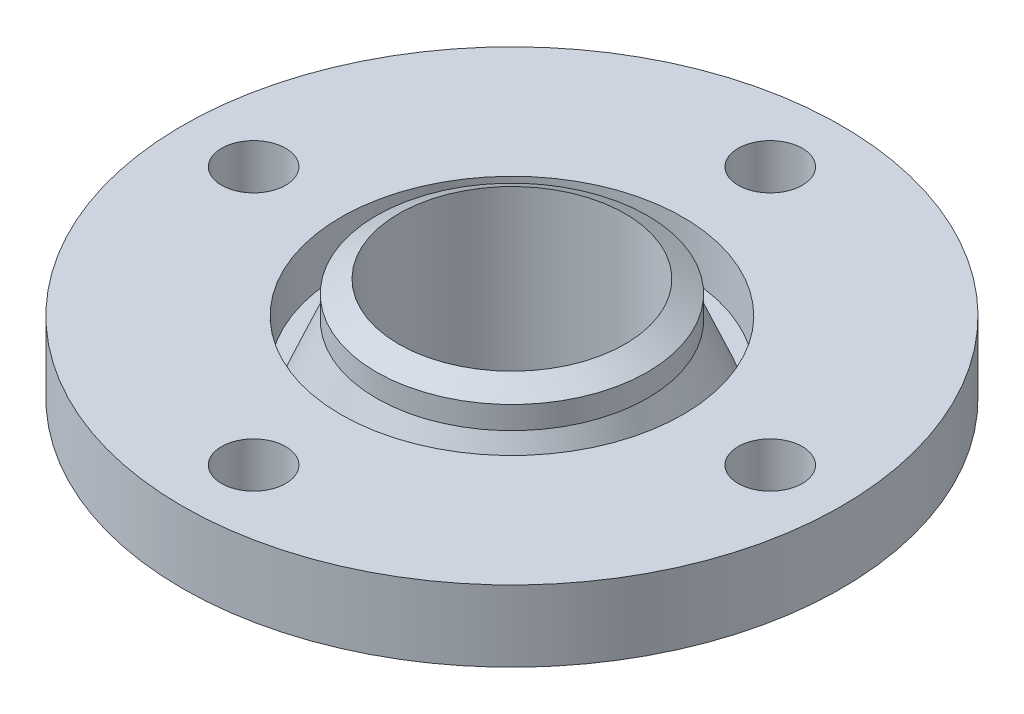
SolidWorks part; units mm, degrees
revolve "BaseRevolve" add sketch "BaseSketch" angle 360 about L0
sketch "BaseSketch" plane through (0, 0, 0) normal (0, 0, 1) x (1, 0, 0)
  line L0 (0, 0) -> (0, -80.3134) construction
  line L1 (-31.75, 0) -> (-31.75, -45)
  line L2 (-31.75, -45) -> (-59, -45)
  line L3 (-59, -45) -> (-59, -29)
  line L4 (-59, -29) -> (-92.5, -29)
  line L5 (-92.5, -29) -> (-92.5, -9)
  line L6 (-92.5, -9) -> (-48, -9)
  line L7 (-48, -9) -> (-48, -23)
  line L8 (-48, -23) -> (-54, -29)
  line L9 (-54, -29) -> (-46, -29)
  line L10 (-46, -29) -> (-38.05, -10)
  line L11 (-38.05, -10) -> (-38.05, -3.6373)
  line L12 (92.5, -29) -> (92.5, -9) construction
  line L13 (59, -45) -> (59, -29) construction
  line L14 (-38.05, -3.6373) -> (-31.75, 0)
  line L15 (38.05, -10) -> (38.05, -3.6373) construction
  line L16 (46, -29) -> (38.05, -10) construction
  line L17 (48, -9) -> (48, -23) construction
  dimension "A1" = 76.1
  dimension "B1" = 96
  dimension "C" = 20
  dimension "DD" = 118
  dimension "D" = 185
  dimension "F" = 16
  dimension "D7" = 45
  dimension "E" = 6
  dimension "S" = 6.3
  dimension "H1" = 10
  dimension "D11" = 60
  dimension "H" = 45
  dimension "N1" = 92
ref_plane "前视" through (0, 0, 0) normal (0, 0, 1) x (1, 0, 0)
ref_plane "上视" through (0, 0, 0) normal (0, 1, 0) x (1, 0, 0)
ref_plane "右视" through (0, 0, 0) normal (1, 0, 0) x (0, 0, -1)
sketch "CutSketch" plane through (0, 0, 0) normal (0, 0, 1) x (1, 0, 0)
  line L0 (-72.5, 10.8054) -> (-72.5, -113.5815) construction
  line L1 (-72.5, -8) -> (-72.5, -30)
  line L2 (-81.5, -8) -> (-72.5, -8)
  line L3 (-81.5, -8) -> (-81.5, -30)
  line L4 (-81.5, -30) -> (-72.5, -30)
  line L5 (92.5, -9) -> (-92.5, -9) construction
  line L6 (-92.5, -29) -> (92.5, -29) construction
  line L7 (-63.5, -8) -> (-63.5, -30) construction
  line L8 (136.4663, 185.4534) -> (135.3473, 181.6131) construction
  line L9 (0, 62.8551) -> (0, -106.7074) construction
  line L10 (72.5, 10.8054) -> (72.5, -113.5815) construction
  dimension "D2" = 1
  dimension "D3" = 1
  dimension "L" = 18
  dimension "K" = 145
revolve "CenterRevCut" cut sketch "CutSketch" angle 360 about L0
ref_axis "PatternAxis" through (0, -29, 0) along (0, 1, 0)
pattern_circular "BoltCirclePattern" count 4 over 360 about axis through (0, 0, 0) along (0, -1, 0) of "CenterRevCut"
equation "\"D1@BoltCirclePattern\"=\"n@CutSketch\""
